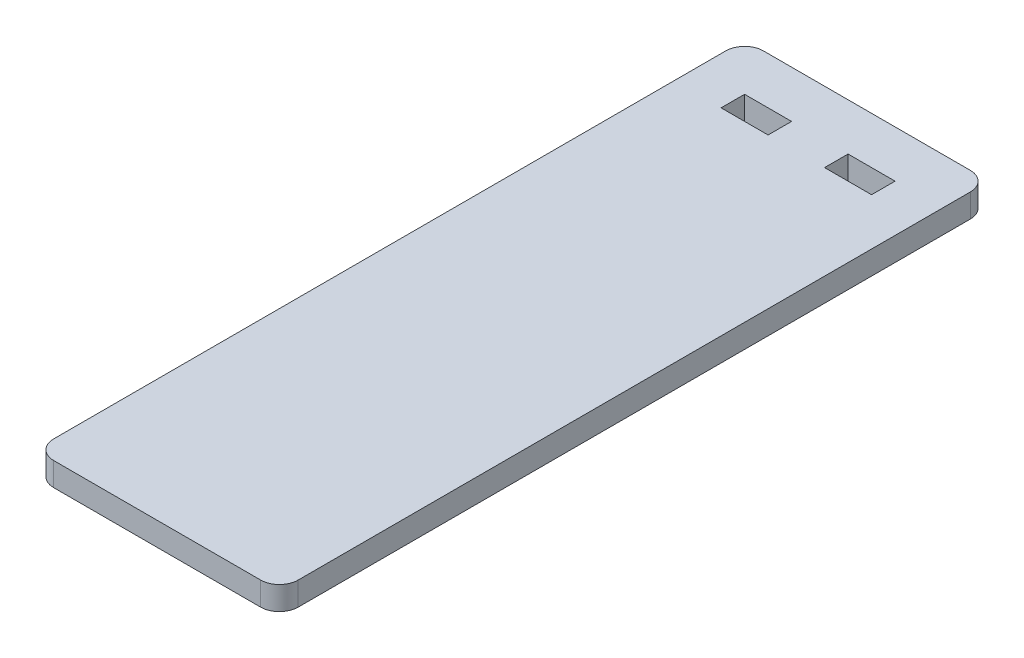
SolidWorks part; units mm, degrees
material "Acrylic (Medium-high impact)"
ref_plane "Front Plane" through (0, 0, 0) normal (0, 0, 1) x (1, 0, 0)
ref_plane "Top Plane" through (0, 0, 0) normal (0, 1, 0) x (1, 0, 0)
ref_plane "Right Plane" through (0, 0, 0) normal (1, 0, 0) x (0, 0, -1)
ref_plane "Plane1" through (0, 0, 0) normal (0, 1, 0) x (1, 0, 0)
sketch "Sketch1" plane through (0, 0, 0) normal (0, 1, 0) x (1, 0, 0)
  line L1 (-26.2811, -39.6588) -> (6.7489, -39.6588)
  line L2 (-26.2811, -39.6588) -> (-26.2811, 56.2162)
  line L3 (-26.2811, 56.2162) -> (6.7489, 56.2162)
  line L4 (6.7489, -39.6588) -> (6.7489, 56.2162)
  dimension "D1" = 95.875
  dimension "D2" = 33.03
extrude "Boss-Extrude1" add sketch "Sketch1" along normal blind 3.175
sketch "Sketch2" plane through (0, 3.175, 0) normal (0, 1, 0) x (1, 0, 0)
  line L0 (-26.2811, 56.2162) -> (-26.2811, -39.6588) construction
  line L1 (-5.9511, 46.6912) -> (0.3989, 46.6912)
  line L2 (-5.9511, 46.6912) -> (-5.9511, 49.8662)
  line L3 (-5.9511, 49.8662) -> (0.3989, 49.8662)
  line L4 (0.3989, 46.6912) -> (0.3989, 49.8662)
  line L5 (-19.9311, 46.6912) -> (-13.5811, 46.6912)
  line L6 (6.7489, 56.2162) -> (-26.2811, 56.2162) construction
  line L7 (6.7489, -39.6588) -> (6.7489, 56.2162) construction
  line L8 (-19.9311, 46.6912) -> (-19.9311, 49.8662)
  line L9 (-19.9311, 49.8662) -> (-13.5811, 49.8662)
  line L10 (-13.5811, 46.6912) -> (-13.5811, 49.8662)
  dimension "D1" = 6.35
  dimension "D2" = 3.175
  dimension "D3" = 6.35
  dimension "D4" = 6.35
  dimension "D5" = 3.175
  dimension "D6" = 6.35
  dimension "D7" = 6.35
  dimension "D8" = 6.35
  dimension "D9" = 7.63
extrude "Cut-Extrude1" cut sketch "Sketch2" against normal through all
fillet "Fillet1" radius 2.54 4 edges at (-26.2811, 1.5875, -56.2162) (6.7489, 1.5875, -56.2162) (6.7489, 1.5875, 39.6588) (-26.2811, 1.5875, 39.6588)
